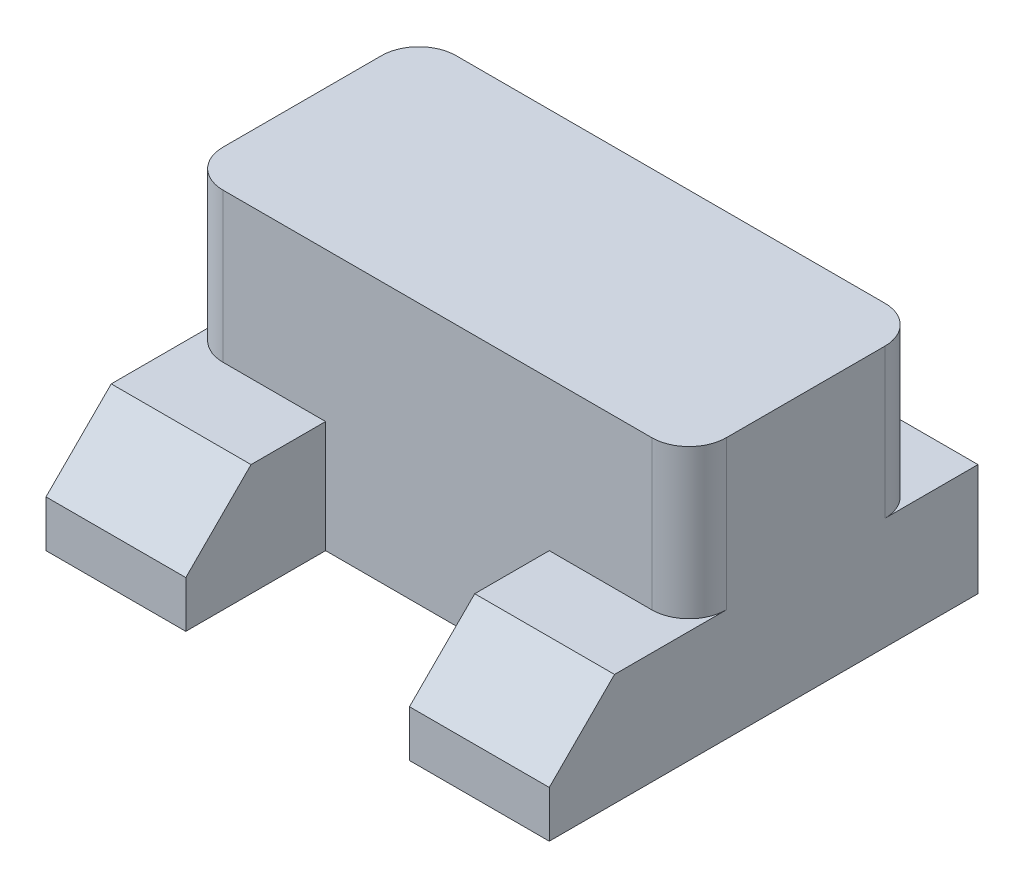
SolidWorks part; units mm, degrees
ref_plane "前视基准面" through (0, 0, 0) normal (0, 0, 1) x (1, 0, 0)
ref_plane "上视基准面" through (0, 0, 0) normal (0, 1, 0) x (1, 0, 0)
ref_plane "右视基准面" through (0, 0, 0) normal (1, 0, 0) x (0, 0, -1)
sketch "草图1" plane through (0, 0, 0) normal (0, 1, 0) x (1, 0, 0)
  line L0 (-2.7, 0.85) -> (-2.7, -0.85)
  line L1 (-2.3, 1.35) -> (2.3, 1.35)
  line L2 (-2.8, 0.85) -> (-2.8, -0.85)
  line L3 (-2.3, -1.35) -> (2.3, -1.35)
  line L4 (2.8, 0.85) -> (2.8, -0.85)
  line L5 (-2.8, 1.35) -> (2.8, -1.35) construction
  line L6 (-2.8, -1.35) -> (2.8, 1.35) construction
  line L7 (-2.3, -1.25) -> (2.3, -1.25)
  line L8 (2.7, 0.85) -> (2.7, -0.85)
  line L9 (-2.3, 1.25) -> (2.3, 1.25)
  arc A0 (2.3, 1.35) -> (2.8, 0.85) centre (2.3, 0.85) cw
  arc A1 (2.3, -1.35) -> (2.8, -0.85) centre (2.3, -0.85) ccw
  arc A2 (-2.8, -0.85) -> (-2.3, -1.35) centre (-2.3, -0.85) ccw
  arc A3 (-2.3, 1.35) -> (-2.8, 0.85) centre (-2.3, 0.85) ccw
  arc A4 (-2.3, 1.25) -> (-2.7, 0.85) centre (-2.3, 0.85) ccw
  arc A5 (-2.7, -0.85) -> (-2.3, -1.25) centre (-2.3, -0.85) ccw
  arc A6 (2.3, -1.25) -> (2.7, -0.85) centre (2.3, -0.85) ccw
  arc A7 (2.3, 1.25) -> (2.7, 0.85) centre (2.3, 0.85) cw
  point P0 (0, 0)
  dimension "D3" = 0.5
  dimension "D1" = 5.6
  dimension "D2" = 2.7
  dimension "D4" = 0.1
extrude "凸台-拉伸3" add sketch "草图1" along normal blind 1.6 and the other way blind 1.2 contours A4 L0 A5 L7 A6 L8 A7 L9
sketch "草图2" plane through (0, 0, 0) normal (0, 1, 0) x (1, 0, 0)
  line L1 (-2.7, 1.25) -> (2.7, 1.25)
  line L2 (-2.7, 1.25) -> (-2.7, -1.25)
  line L3 (-2.7, -1.25) -> (2.7, -1.25)
  line L4 (2.7, 1.25) -> (2.7, -1.25)
  line L5 (-2.7, 1.25) -> (2.7, -1.25) construction
  line L6 (-2.7, -1.25) -> (2.7, 1.25) construction
  point P0 (0, 0)
  dimension "D1" = 5.4
  dimension "D2" = 2.5
extrude "凸台-拉伸4" add sketch "草图2" against normal blind 1.2
ref_plane "基准面4" through (0, 0, -1.25) normal (0, 0, -1) x (-1, 0, 0)
ref_plane "基准面5" through (0, 0, 1.25) normal (0, 0, 1) x (1, 0, 0)
ref_plane "基准面6" through (0, -1.2, 0) normal (0, -1, 0) x (-1, 0, 0)
sketch "草图5" plane through (0, -1.2, 0) normal (0, -1, 0) x (-1, 0, 0)
  line L1 (2, 0.9) -> (-2, 0.9)
  line L2 (2, 0.9) -> (2, -0.6)
  line L3 (2, -0.6) -> (-2, -0.6)
  line L4 (-2, 0.9) -> (-2, -0.6)
  point P6 (0, -0.6)
  dimension "D1" = 4
  dimension "D2" = 1.5
extrude "凸台-拉伸7" add sketch "草图5" along normal blind 0.5
sketch "草图6" plane through (0, 0, -1.25) normal (0, 0, -1) x (-1, 0, 0)
  line L0 (-2, -1.2) -> (2, -1.2) construction
  line L1 (2.7, 0) -> (1.2, 0)
  line L2 (2.7, 0) -> (2.7, -1.2)
  line L3 (2.7, -1.2) -> (1.2, -1.2)
  line L4 (1.2, 0) -> (1.2, -1.2)
  line L5 (2.7, -1.2) -> (-2.7, -1.2) construction
  line L6 (-2.7, 0) -> (-1.2, 0)
  line L7 (-2.7, 0) -> (-2.7, -1.2)
  line L8 (-2.7, -1.2) -> (-1.2, -1.2)
  line L9 (-1.2, 0) -> (-1.2, -1.2)
  dimension "D1" = 2.4
extrude "凸台-拉伸8" add sketch "草图6" along normal blind 0.6
sketch "草图7" plane through (0, 0, 1.25) normal (0, 0, 1) x (1, 0, 0)
  line L4 (2.7, 0) -> (1.2, 0)
  line L5 (1.2, 0) -> (1.2, -1.2)
  line L6 (1.2, -1.2) -> (2.7, -1.2)
  line L7 (2.7, -1.2) -> (2.7, 0)
  line L8 (2.7, 0) -> (1.2, 0)
  line L9 (1.2, 0) -> (1.2, -1.2)
  line L10 (1.2, -1.2) -> (2.7, -1.2)
  line L11 (2.7, -1.2) -> (2.7, 0)
  line L12 (-1.2, 0) -> (-2.7, 0)
  line L13 (-1.2, -1.2) -> (-1.2, 0)
  line L14 (-2.7, -1.2) -> (-1.2, -1.2)
  line L15 (-2.7, 0) -> (-2.7, -1.2)
  line L16 (-1.2, 0) -> (-2.7, 0)
  line L17 (-1.2, -1.2) -> (-1.2, 0)
  line L18 (-2.7, -1.2) -> (-1.2, -1.2)
  line L19 (-2.7, 0) -> (-2.7, -1.2)
  dimension "D1" = 0
  dimension "D2" = 0
extrude "凸台-拉伸9" add sketch "草图7" along normal blind 1.5
chamfer "倒角2" distance 0.7 angle 45 2 edges at (-1.95, 0, 2.75) (1.95, 0, 2.75)
